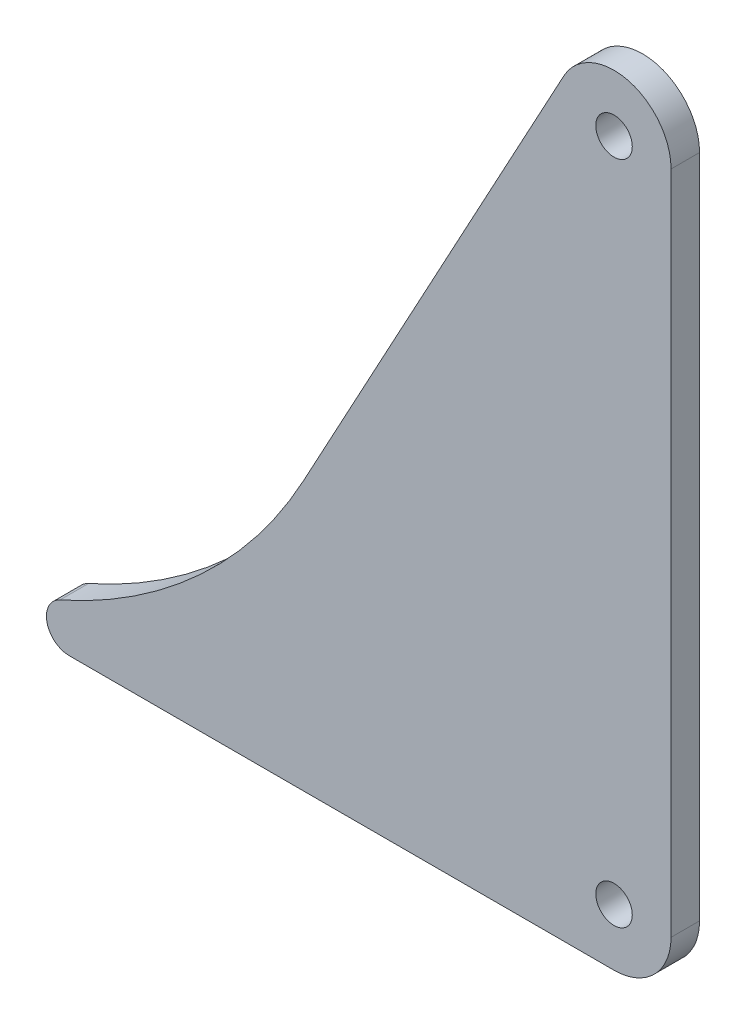
SolidWorks part; units mm, degrees
ref_plane "Front Plane" through (0, 0, 0) normal (0, 0, 1) x (1, 0, 0)
ref_plane "Top Plane" through (0, 0, 0) normal (0, 1, 0) x (1, 0, 0)
ref_plane "Right Plane" through (0, 0, 0) normal (1, 0, 0) x (0, 0, -1)
sketch "Sketch1" plane through (0, 0, 0) normal (0, 0, 1) x (1, 0, 0)
  line L0 (0, 0) -> (0, 105.5171)
  line L1 (0, 0) -> (-88.9, 0)
  line L2 (0, 105.5171) -> (-40.9364, 29.9179)
  line L4 (131.6519, 348.6446) -> (-15.875, 76.2) construction
  arc A0 (-88.9, 0) -> (-40.9364, 29.9179) centre (-91.2397, 57.1568) ccw
  point P6 (-40.9364, 29.9179)
  point P7 (0, 105.5171)
  dimension "D2" = 88.9
extrude "Boss-Extrude1" add sketch "Sketch1" along normal blind 3.175
fillet "Fillet1" radius 2.54 1 edges at (-88.9, 0, 1.5875)
fillet "Fillet2" radius 6.35 2 edges at (0, 0, 1.5875) (0, 105.5171, 1.5875)
sketch "Sketch2" plane through (0, 0, 3.175) normal (0, 0, 1) x (1, 0, 0)
  circle A0 centre (-6.35, 6.35) radius 2.032
  circle A1 centre (-6.35, 80.4545) radius 2.032
  arc A2 (0, 80.4545) -> (-11.9339, 83.4782) centre (-6.35, 80.4545) ccw construction
  arc A3 (-6.35, 0) -> (0, 6.35) centre (-6.35, 6.35) ccw construction
  dimension "D3" = 4.064
extrude "Cut-Extrude1" cut sketch "Sketch2" against normal through all
